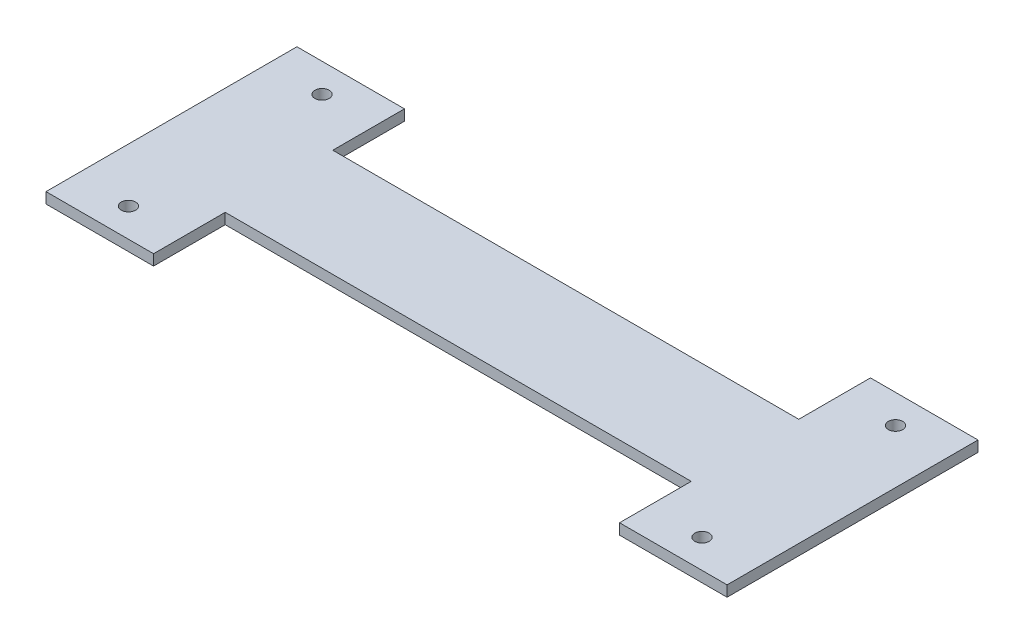
SolidWorks part; units mm, degrees
material "Caoba"
ref_plane "Alzado" through (0, 0, 0) normal (0, 0, 1) x (1, 0, 0)
ref_plane "Planta" through (0, 0, 0) normal (0, 1, 0) x (1, 0, 0)
ref_plane "Vista lateral" through (0, 0, 0) normal (1, 0, 0) x (0, 0, -1)
sketch "Croquis1" plane through (0, 0, 0) normal (0, 1, 0) x (1, 0, 0)
  line L1 (0, 0) -> (190, 0)
  line L2 (0, 0) -> (0, -70)
  line L3 (0, -70) -> (190, -70)
  line L4 (190, 0) -> (190, -70)
  dimension "D1" = 190
  dimension "D2" = 70
extrude "Saliente-Extruir1" add sketch "Croquis1" along normal blind 3
sketch "Croquis2" plane through (0, 3, 0) normal (0, 1, 0) x (1, 0, 0)
  line L0 (95, 0) -> (95, -70) construction
  line L1 (190, 0) -> (0, 0) construction
  line L2 (0, -70) -> (190, -70) construction
  line L3 (0, -35) -> (190, -35) construction
  line L4 (0, 0) -> (0, -70) construction
  line L5 (190, -70) -> (190, 0) construction
  line L6 (30, 0) -> (160, 0)
  line L7 (30, -50) -> (160, -50)
  line L8 (30, -50) -> (30, -70)
  line L9 (30, -70) -> (160, -70)
  line L10 (160, -50) -> (160, -70)
  line L11 (160, -20) -> (160, 0)
  line L12 (30, -20) -> (160, -20)
  line L13 (30, -20) -> (30, 0)
  circle A0 centre (15, -8) radius 2
  circle A1 centre (175, -8) radius 2
  circle A2 centre (175, -62) radius 2
  circle A3 centre (15, -62) radius 2
  dimension "D1" = 54
  dimension "D2" = 54
  dimension "D3" = 4
  dimension "D4" = 4
  dimension "D5" = 4
  dimension "D6" = 4
  dimension "D7" = 160
  dimension "D8" = 160
  dimension "D9" = 80
  dimension "D10" = 27
  dimension "D11" = 80
  dimension "D12" = 27
  dimension "D13" = 30
  dimension "D14" = 30
  dimension "D15" = 20
extrude "Cortar-Extruir1" cut sketch "Croquis2" against normal blind 3
